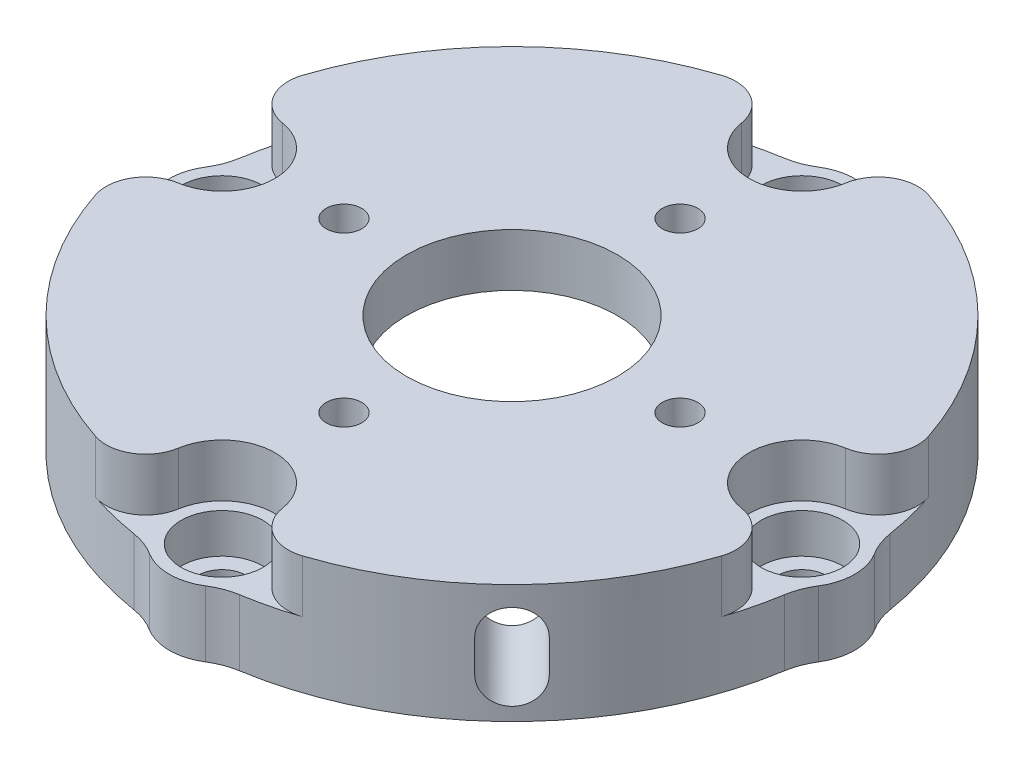
SolidWorks part; units mm, degrees
ref_plane "Front Plane" through (0, 0, 0) normal (0, 0, 1) x (1, 0, 0)
ref_plane "Top Plane" through (0, 0, 0) normal (0, 1, 0) x (1, 0, 0)
ref_plane "Right Plane" through (0, 0, 0) normal (1, 0, 0) x (0, 0, -1)
sketch "Sketch1" plane through (0, 0, 0) normal (0, 1, 0) x (1, 0, 0)
  circle A0 centre (0, 0) radius 25
  circle A1 centre (0, 0) radius 8
  dimension "D1" = 50
  dimension "D2" = 16
extrude "Boss-Extrude1" add sketch "Sketch1" against normal blind 4
sketch "Sketch2" plane through (0, -4, 0) normal (0, -1, 0) x (1, 0, 0)
  circle A0 centre (0, 0) radius 25
  circle A1 centre (0, 0) radius 25 construction
  circle A2 centre (0, 0) radius 17.5
  dimension "D1" = 35
extrude "Boss-Extrude4" add sketch "Sketch2" along normal blind 5
sketch "Sketch4" plane through (0, -9, 0) normal (0, -1, 0) x (1, 0, 0)
  circle A0 centre (0, 0) radius 22 construction
  circle A1 centre (0, 22) radius 3.1
  circle A2 centre (0, 22) radius 1.85
  circle A3 centre (0, 22) radius 4
  circle M7 centre (0, 0) radius 25
  dimension "D1" = 44
  dimension "D2" = 6.2
  dimension "D3" = 3.7
  dimension "D4" = 8
extrude "Boss-Extrude2" add sketch "Sketch4" against normal blind 5 contours A3 A1 M7 | A3 A1 M7 region at (2.5535, -9, 23.939) region at (0, -9, 25.383)
extrude "Boss-Extrude3" add sketch "Sketch4<5>" against normal blind 2 contours A2 A1 | A2 A1 region at (-3.0123, -9, 22)
sketch "Sketch4<5>" plane through (0, -9, 0) normal (0, -1, 0) x (1, 0, 0) same geometry as "Sketch4"
extrude "Cut-Extrude3" cut sketch "Sketch4<6>" against normal through all from surface contours A1 A2 M7 region at (-1.8221, -9, 19.6004) starting at face at (0, -7, 25.05)
sketch "Sketch4<6>" plane through (0, -9, 0) normal (0, -1, 0) x (1, 0, 0) same geometry as "Sketch4"
extrude "Cut-Extrude4" cut sketch "Sketch4<7>" against normal through all contours A2 | A2 region at (0, -9, 22)
sketch "Sketch4<7>" plane through (0, -9, 0) normal (0, -1, 0) x (1, 0, 0) same geometry as "Sketch4"
extrude "Cut-Extrude9" cut sketch "Sketch4<9>" against normal through all from surface contours A3 A1 M7 region at (2.5535, -9, 23.939) starting at face at (0, -4, 25.2416)
sketch "Sketch4<9>" plane through (0, -9, 0) normal (0, -1, 0) x (1, 0, 0) same geometry as "Sketch4"
sketch "Sketch5" plane through (0, 0, 0) normal (0, 1, 0) x (1, 0, 0)
  line L1 (2.3671, 12.75) -> (1.1836, 14.8)
  line L2 (1.1836, 14.8) -> (-1.1836, 14.8)
  line L3 (-1.1836, 14.8) -> (-2.3671, 12.75)
  line L4 (-2.3671, 12.75) -> (-1.1836, 10.7)
  line L5 (-1.1836, 10.7) -> (1.1836, 10.7)
  line L6 (1.1836, 10.7) -> (2.3671, 12.75)
  circle A0 centre (0, 0) radius 12.75 construction
  circle A1 centre (0, 12.75) radius 1.35
  circle A2 centre (0, 12.75) radius 2.05 construction
  dimension "D1" = 25.5
  dimension "D2" = 2.7
  dimension "D3" = 4.1
extrude "Cut-Extrude5" cut sketch "Sketch5" against normal up to next contours A1 region at (0, 0, -12.75)
extrude "Cut-Extrude7" cut sketch "Sketch5<4>" along normal blind 2 from surface starting at face at (0, -4, -11.4)
sketch "Sketch5<4>" plane through (0, 0, 0) normal (0, 1, 0) x (1, 0, 0) same geometry as "Sketch5"
fillet "Fillet5" radius 3 2 edges at (-2.8159, -2, 24.8409) (2.8159, -2, 24.8409)
fillet "Fillet4" radius 5 2 edges at (2.8159, -6.5, 24.8409) (-2.8159, -6.5, 24.8409)
pattern_circular "CirPattern1" count 4 over 360 about axis through (0, -4, 0) along (0, 1, 0) of "Boss-Extrude2", "Boss-Extrude3", "Cut-Extrude3", "Cut-Extrude4", "Cut-Extrude9", "Cut-Extrude5", "Cut-Extrude7", "Fillet5", "Fillet4" reverse direction yes
ref_plane "Plane2" through (6.375, 0, 6.375) normal (0.7071, 0, 0.7071) x (0.7071, 0, -0.7071)
sketch "Sketch7" plane through (6.375, 0, 6.375) normal (0.7071, 0, 0.7071) x (0.7071, 0, -0.7071)
  line L0 (0, -6) -> (0, -3.5) construction
  line L1 (0, -9) -> (0, -4) construction
  line L2 (-2, -6) -> (-2, -3.5)
  line L3 (2, -6) -> (2, -3.5)
  line L4 (28.6, 0) -> (-28.6, 0) construction
  arc A0 (-2, -6) -> (2, -6) centre (0, -6) ccw
  arc A1 (2, -3.5) -> (-2, -3.5) centre (0, -3.5) ccw
  point P5 (0, -4.75)
  dimension "D1" = 2
  dimension "D3" = 2.5
  dimension "D2" = 3.5
extrude "Cut-Extrude8" cut sketch "Sketch7" along normal up to next and the other way up to next
equation "\"D2@Sketch7\"=\"D1@Sketch7\"+1.5"
